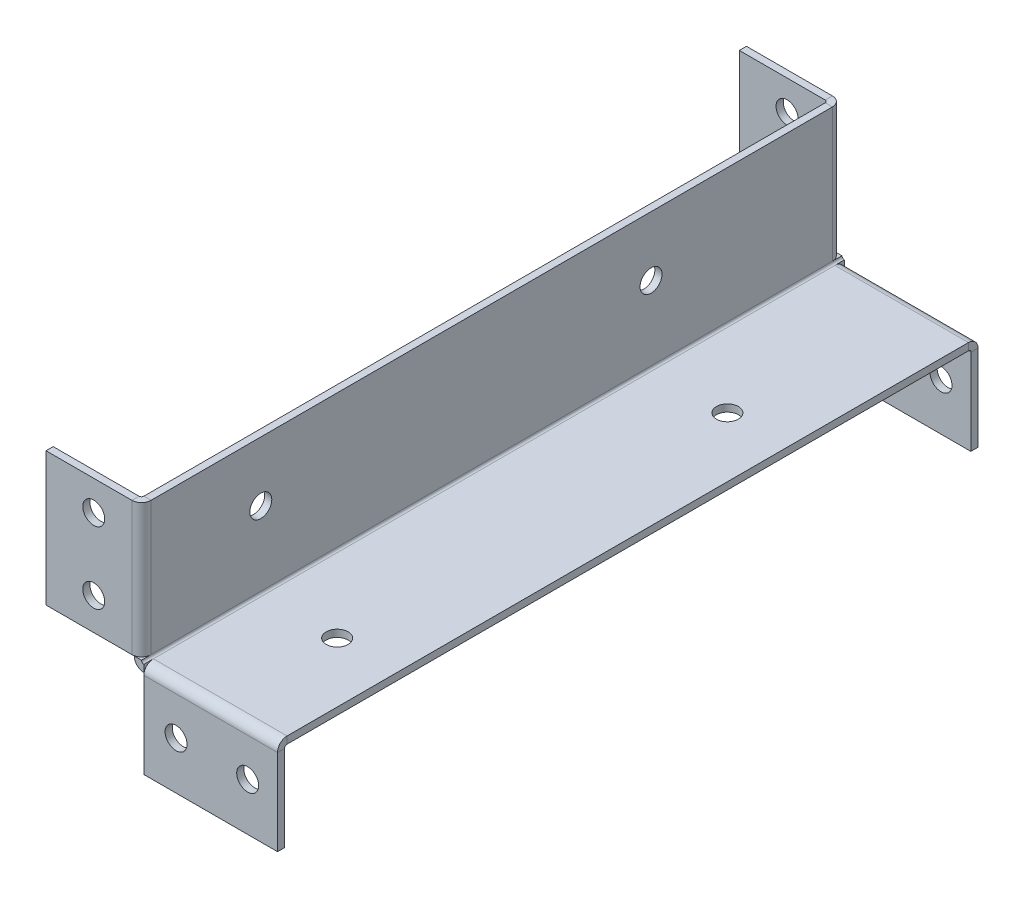
SolidWorks part; units mm, degrees
note: The reader was unsure of these and kept them because the rebuilt part matched: flange length of "Edge-Flange1", "Edge-Flange2".
ref_plane "Front Plane" through (0, 0, 0) normal (0, 0, 1) x (1, 0, 0)
ref_plane "Top Plane" through (0, 0, 0) normal (0, 1, 0) x (1, 0, 0)
ref_plane "Right Plane" through (0, 0, 0) normal (1, 0, 0) x (0, 0, -1)
sketch "Sketch1" plane through (0, 0, 0) normal (0, 1, 0) x (1, 0, 0)
  line L1 (30, 146.75) -> (-30, 146.75)
  line L2 (30, 146.75) -> (30, -146.75)
  line L3 (30, -146.75) -> (-30, -146.75)
  line L4 (-30, 146.75) -> (-30, -146.75)
  line L5 (30, 146.75) -> (-30, -146.75) construction
  line L6 (30, -146.75) -> (-30, 146.75) construction
  point P0 (0, 0)
  dimension "D1" = 60
  dimension "D2" = 293.5
sheet metal parameters "Sheet-Metal1" thickness 3 parameters "D1"=1
base flange "Base-Flange1" sketch "Sketch1" thickness 3 reverse thickness direction yes parameters "D1"=1
edge flange "Edge-Flange1" sketch "Sketch5" flange angle 90 flange length 60 flange position material inside bend radius 1 thickness 3 parameters "D6"=10
sketch "Sketch5" plane through (-30, 3, 0) normal (-1, 0, 0) x (0, 0, 1)
  line L2 (-146.75, 0) -> (-146.75, 57)
  line L3 (-146.75, 57) -> (146.75, 57)
  line L4 (146.75, 57) -> (146.75, 0)
  line L5 (-146.75, 0) -> (146.75, 0) construction
  line L6 (-146.75, 0) -> (146.75, 0)
bend "EdgeBend1" bend radius 1 bend angle 90 parameters "D5"=1
edge flange "Edge-Flange2" sketch "Sketch14" flange profiles "Sketch14", "Sketch15", "Sketch16", "Sketch17" flange angle 90 flange length 40 flange position material inside bend radius 1 thickness 3 relief none parameters "D6"=10, "D8"=0.5
sketch "Sketch14" plane through (-30, 0, 146.75) normal (0, 0, -1) x (0, -1, 0)
  line L1 (-4, 0) -> (-60, 0) construction
  line L2 (-60, 0) -> (-60, 37)
  line L3 (-60, 37) -> (-4, 37)
  line L4 (-4, 37) -> (-4, 0)
  line L5 (-4, 0) -> (-60, 0)
sketch "Sketch15" plane through (0, 0, 146.75) normal (0, 0, -1) x (1, 0, 0)
  line L0 (30, 0) -> (-26, 0) construction
  line L1 (30, 0) -> (-26, 0)
  line L2 (30, 0) -> (30, 37)
  line L3 (30, 37) -> (-26, 37)
  line L4 (-26, 37) -> (-26, 0)
sketch "Sketch16" plane through (-30, 0, -146.75) normal (0, 0, 1) x (0, 1, 0)
  line L0 (60, 0) -> (4, 0) construction
  line L1 (60, 0) -> (4, 0)
  line L2 (60, 0) -> (60, 37)
  line L3 (60, 37) -> (4, 37)
  line L4 (4, 37) -> (4, 0)
sketch "Sketch17" plane through (0, 0, -146.75) normal (0, 0, 1) x (-1, 0, 0)
  line L0 (26, 0) -> (-30, 0) construction
  line L1 (26, 0) -> (-30, 0)
  line L2 (26, 0) -> (26, 37)
  line L3 (26, 37) -> (-30, 37)
  line L4 (-30, 37) -> (-30, 0)
bend "EdgeBend2" bend radius 1 bend angle 90 parameters "D5"=2
bend "EdgeBend3" bend radius 1 bend angle 90 parameters "D5"=3
bend "EdgeBend4" bend radius 1 bend angle 90 parameters "D5"=4
bend "EdgeBend5" bend radius 1 bend angle 90 parameters "D5"=5
sketch "Sketch18" plane through (0, 0, 146.75) normal (0, 0, 1) x (1, 0, 0)
  line L0 (-26, 3) -> (30, 3) construction
  line L1 (-27, 60) -> (-27, 4) construction
  line L2 (-67, 60) -> (-31, 60) construction
  line L3 (30, -1) -> (30, -37) construction
  circle A0 centre (-47, 47.5) radius 4.6
  circle A1 centre (-47, 17.5) radius 4.6
  circle A2 centre (-12.5, -17) radius 4.6
  circle A3 centre (17.5, -17) radius 4.6
  dimension "D7" = 9.2
  dimension "D1" = 30
  dimension "D2" = 30
  dimension "D3" = 20
  dimension "D4" = 20
  dimension "D5" = 12.5
  dimension "D6" = 12.5
extrude "Extrude1" cut sketch "Sketch18" against normal through all normal cut yes
sketch "Sketch19" plane through (-27, 0, 0) normal (1, 0, 0) x (0, 0, -1)
  line L0 (-142.75, 60) -> (142.75, 60) construction
  line L1 (-146.75, 4) -> (-146.75, 60) construction
  line L2 (146.75, 4) -> (146.75, 60) construction
  circle A0 centre (-96.75, 35) radius 4.6
  circle A1 centre (66.75, 35) radius 4.6
  dimension "D4" = 9.2
  dimension "D2" = 80
  dimension "D3" = 50
  dimension "D1" = 25
extrude "Extrude2" cut sketch "Sketch19" against normal blind 3 normal cut yes
sketch "Sketch20" plane through (0, 3, 0) normal (0, 1, 0) x (1, 0, 0)
  line L0 (30, -142.75) -> (30, 142.75) construction
  line L1 (-26, -146.75) -> (30, -146.75) construction
  line L2 (30, 146.75) -> (-26, 146.75) construction
  circle A0 centre (5, 66.75) radius 4.6
  circle A1 centre (5, -96.75) radius 4.6
  dimension "D2" = 9.2
  dimension "D4" = 80
  dimension "D3" = 50
  dimension "D1" = 25
extrude "Extrude3" cut sketch "Sketch20" against normal blind 3 normal cut yes
flat pattern "Flat-Pattern1" [suppressed]
sketch "Bend-Lines1" plane through (0, 4, 0) normal (0, 1, 0) x (-1, 0, 0)
  line L0 (25, -126.4012) -> (-30, -126.4012) construction
  line L1 (82.8023, -126.4012) -> (27.8023, -126.4012) construction
  line L2 (-30, 126.4012) -> (25, 126.4012) construction
  line L3 (27.8023, 126.4012) -> (82.8023, 126.4012) construction
  line L4 (26.4012, -130) -> (26.4012, 130) construction
  line L5 (25, -126.4012) -> (-30, -126.4012) construction
  line L6 (82.8023, -126.4012) -> (27.8023, -126.4012) construction
  line L7 (-30, 126.4012) -> (25, 126.4012) construction
  line L8 (27.8023, 126.4012) -> (82.8023, 126.4012) construction
  line L9 (26.4012, -130) -> (26.4012, 130) construction
bend of the flat pattern "Flatten-<EdgeBend1>1"
bend of the flat pattern "Flatten-<EdgeBend2>1"
bend of the flat pattern "Flatten-<EdgeBend3>1"
bend of the flat pattern "Flatten-<EdgeBend4>1"
bend of the flat pattern "Flatten-<EdgeBend5>1"
